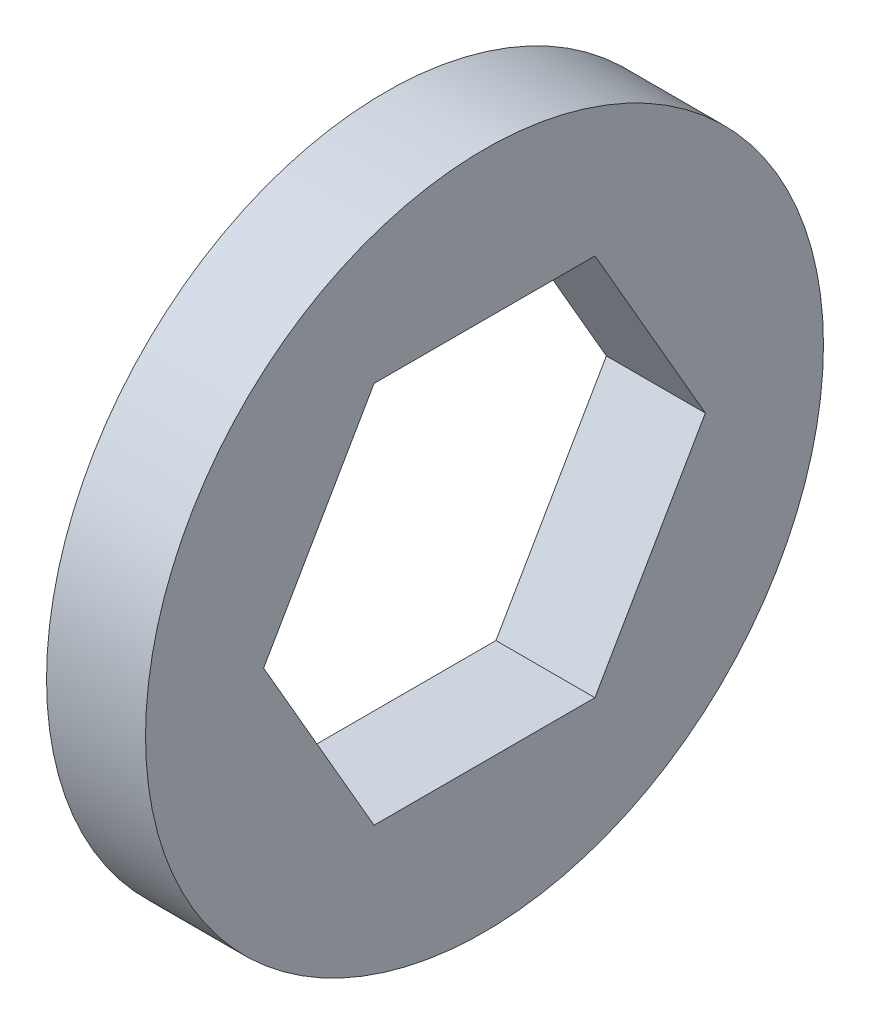
SolidWorks part; units mm, degrees
material "PET"
ref_plane "Front Plane" through (0, 0, 0) normal (0, 0, 1) x (1, 0, 0)
ref_plane "Top Plane" through (0, 0, 0) normal (0, 1, 0) x (1, 0, 0)
ref_plane "Right Plane" through (0, 0, 0) normal (1, 0, 0) x (0, 0, -1)
sketch "Sketch1" plane through (0, 0, 0) normal (1, 0, 0) x (0, 0, -1)
  line L1 (-5.7926, 0) -> (-2.8963, -5.0165)
  line L2 (-2.8963, -5.0165) -> (2.8963, -5.0165)
  line L3 (2.8963, -5.0165) -> (5.7926, 0)
  line L4 (5.7926, 0) -> (2.8963, 5.0165)
  line L5 (2.8963, 5.0165) -> (-2.8963, 5.0165)
  line L6 (-2.8963, 5.0165) -> (-5.7926, 0)
  circle A1 centre (0, 0) radius 8.89
  circle A2 centre (0, 0) radius 5.0165 construction
  point P1 (0, 0)
  dimension "D1" = 10.033
  dimension "D2" = 17.78
extrude "Boss-Extrude1" add sketch "Sketch1" along normal mid plane 2.5959
